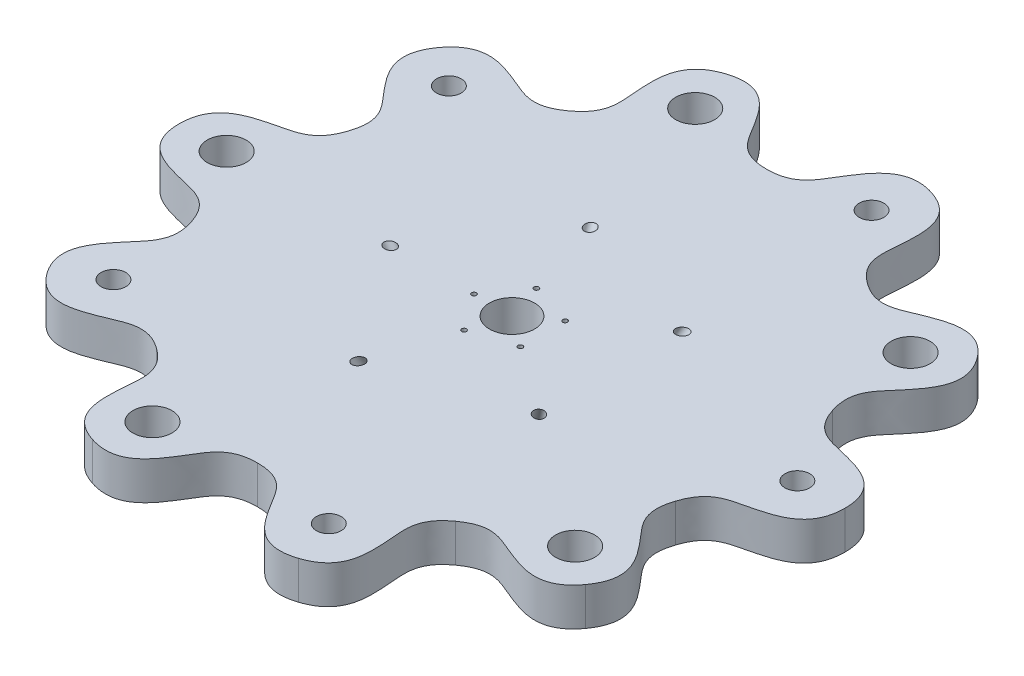
SolidWorks part; units mm, degrees
other "Markup1"
sketch "Sketch22" plane through (67.4, 16.5, 67.4) normal (0.6133, 0.6241, 0.4841) x (0.6587, -0.0661, -0.7495)
sketch "Sketch37" plane through (67.4, 28, 67.4) normal (0.6133, 0.6241, 0.4841) x (0.6587, -0.0661, -0.7495)
other "Markup2"
sketch "Sketch23" plane through (67.4, 26.5, 67.4) normal (0.1362, 0.0894, 0.9866) x (0.9893, -0.0646, -0.1307)
sketch "Sketch38" plane through (67.4, 28, 67.4) normal (0.1362, 0.0894, 0.9866) x (0.9893, -0.0646, -0.1307)
other "Markup5"
sketch "Sketch28" plane through (-67.4, 30.5, 67.4) normal (-0.0176, 0.5562, 0.8308) x (0.9998, 0.0146, 0.0115)
sketch "Sketch39" plane through (-67.4, 28, 67.4) normal (-0.0176, 0.5562, 0.8308) x (0.9998, 0.0146, 0.0115)
material "1023 Carbon Steel Sheet (SS)"
ref_plane "Front Plane" through (0, 0, 0) normal (0, 0, 1) x (1, 0, 0)
ref_plane "Top Plane" through (0, 0, 0) normal (0, 1, 0) x (1, 0, 0)
ref_plane "Right Plane" through (0, 0, 0) normal (1, 0, 0) x (0, 0, -1)
sketch "Sketch1" plane through (0, 0, 0) normal (0, 0, 1) x (1, 0, 0)
  line L5 (-47.4, 0) -> (-47.4, -8)
  line L9 (-7, -8) -> (0, -8)
  line L10 (0, -8) -> (0, 0)
  line L12 (-7, -8) -> (-17.4, -8)
  line L24 (-17.4, -8) -> (-47.4, -8)
  line L25 (-47.4, 0) -> (0, 0)
  dimension "D2" = 8
  dimension "D3" = 47.4
  dimension "D8" = 0
  dimension "D10" = 7
revolve "Revolve1" add sketch "Sketch1" angle 360 about L10
sketch "Sketch4" plane through (0, 0, 0) normal (0, 0, 1) x (1, 0, 0)
  line L0 (0, 0) -> (0, 13.3666) construction
sketch "Sketch2" plane through (0, 0, 0) normal (0, 1, 0) x (1, 0, 0)
  circle A0 centre (-8, 0) radius 0.5
  dimension "D2" = 1
  dimension "D1" = 8
extrude "Fuel holes" cut sketch "Sketch2" against normal up to next from offset 5
pattern_circular "CirPattern1" count 5 over 360 about axis through (0, 0, 0) along (0, 1, 0) of "Fuel holes" reverse direction yes
sketch "Sketch5" plane through (0, 0, 0) normal (1, 0, 0) x (0, 0, -1)
sketch "Sketch19" plane through (0, -8, 0) normal (0, -1, 0) x (1, 0, 0)
  line L0 (-47.4, 0) -> (-70, 0) construction
  line L1 (-56.6312, -41.145) -> (0, 0) construction
  line L4 (0, 0) -> (-66.574, -21.6312) construction
  line L5 (-51.8483, -13.5569) -> (-50.8815, -16.5324) construction
  line L9 (-69, 0) -> (-70, 0)
  line L11 (-53.7996, 39.0877) -> (-54.2257, 38.5013)
  circle A1 centre (0, 0) radius 47.4
  circle A2 centre (0, 0) radius 70 construction
  circle A3 centre (-60, 0) radius 4.1
  circle A4 centre (0, 0) radius 47.4 construction
  circle A5 centre (-48.541, -35.2671) radius 2.6
  circle A6 centre (0, 0) radius 53.5
  circle A8 centre (0, 0) radius 70
  spline S0 degree 3 poles (-50.8815, -16.5324) (-52.4491, -11.7078) (-59.9998, -9.5551) (-70, -7.7496) (-70, 0) knots 0 0 0 0 0.376166 1 1 1 1
  spline S1 degree 3 poles (-50.8815, -16.5324) (-49.3139, -21.357) (-54.1572, -27.5367) (-61.1863, -34.8754) (-56.6312, -41.145) knots 0 0 0 0 0.376166 1 1 1 1
  circle M22 centre (0, 0) radius 47.4
  dimension "D2" = 8.2
  dimension "D5" = 5.2
  dimension "D7" = 107
  dimension "D3" = 60
  dimension "D4" = 36
  dimension "D6" = 60
  dimension "D8" = 18
  dimension "D1" = 22.6
extrude "Boss-Extrude2" add sketch "Sketch19" against normal blind 8 contours A6 S1 A8 S0 A3 A5 | S1 S0 A8 | A3 | A5 | A6 M22 region at (-60, -8, 0) region at (-48.541, -8, -35.2671) region at (8.1325, -8, -51.3467) region at (-61.1052, -8, -7.4539) region at (-60.0877, -8, -19.5238)
extrude "Bolt holes" cut sketch "Sketch19<3>" against normal up to surface (8 mm away) contours A3 | A5 up to face at (-1.9721, 0, -7.6085)
sketch "Sketch19<3>" plane through (0, -8, 0) normal (0, -1, 0) x (1, 0, 0) same geometry as "Sketch19"
extrude "Grooves" cut sketch "Sketch19<8>" against normal through all contours S1 S0 A8 region at (-60.0877, -8, -19.5238)
sketch "Sketch19<8>" plane through (0, -8, 0) normal (0, -1, 0) x (1, 0, 0) same geometry as "Sketch19"
sketch "Sketch21" plane through (0, 0, 0) normal (0, 0, 1) x (1, 0, 0)
  line L0 (0, 0) -> (51.8972, 0) construction
  line L1 (0, 0) -> (0, -5.4672) construction
sketch "Sketch8" plane through (-29.8564, -8, 0) normal (0, -1, 0) x (-1, 0, 0)
  line L0 (-29.8564, 0) -> (-8.8564, 0) construction
  line L1 (-8.8564, 0) -> (-8.8564, 32.0516) construction
  circle A2 centre (-8.8564, 0) radius 1.75
  dimension "D1" = 3.5
  dimension "D2" = 21
ref_plane "Plane1" through (-21, 0, 0) normal (1, 0, 0) x (0, 0, -1)
ref_plane "Plane2" through (-1.7859, 3.0933, 0) normal (0.5, -0.866, 0) x (0, 0, -1)
sketch "Sketch41" plane through (-1.7859, 3.0933, 0) normal (0.5, -0.866, 0) x (0, 0, -1)
  circle A0 centre (0, -22.1865) radius 1.15
  dimension "D1" = 2.3
extrude "Cut-Extrude7" cut sketch "Sketch41" against normal blind 10 and the other way through all
sketch "Sketch31" plane through (0, -8, 0) normal (0, -1, 0) x (1, 0, 0)
  circle A0 centre (0, 0) radius 27.4
  dimension "D1" = 54.8
sketch "Sketch32" plane through (0, 0, 0) normal (0, 1, 0) x (1, 0, 0)
  circle A0 centre (0, 0) radius 5.5 construction
  circle A1 centre (0, 0) radius 4.75
  dimension "M11_threads" = 11
  dimension "M11Tap" = 9.5
sketch "Sketch35" plane through (0, 0, 0) normal (0, 0, 1) x (1, 0, 0)
  line L0 (0, 0) -> (0, 22.3821) construction
pattern_circular "CirPattern9" count 5 over 360 about axis through (0, 0, 0) along (0, 1, 0) of "Cut-Extrude7"
pattern_circular "CirPattern10" count 5 over 360 about axis through (0, 0, 0) along (0, 1, 0) of "Bolt holes"
pattern_circular "CirPattern11" count 10 over 360 about axis through (0, 0, 0) along (0, 1, 0) of "Grooves"
extrude "M11Tap" cut sketch "Sketch32" against normal through all contours A1
equation "\"Bolts\"= 10"
equation "\"D4@Sketch19\"=360/\"Bolts\""
equation "\"D7@Sketch19\"=102+2.5*2"
equation "\"D8@Sketch19\"=\"D4@Sketch19\"/2"
